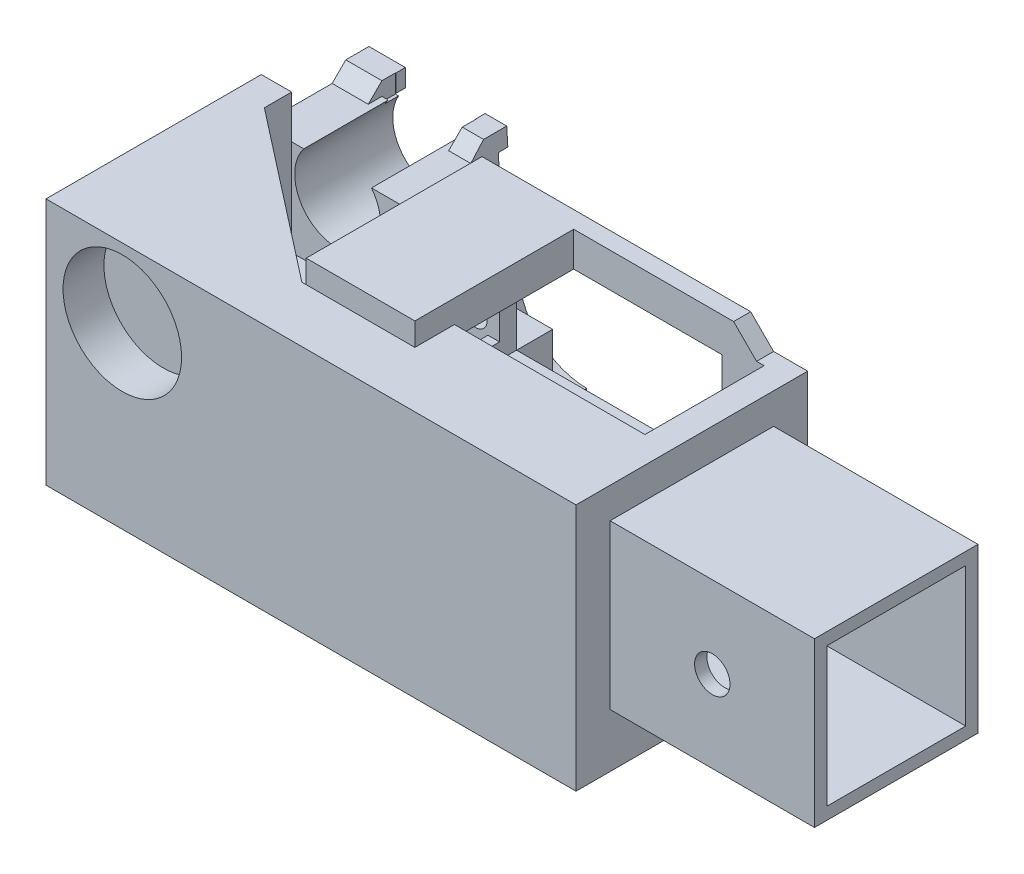
SolidWorks part; units mm, degrees
ref_plane "Front Plane" through (0, 0, 0) normal (0, 0, 1) x (1, 0, 0)
ref_plane "Top Plane" through (0, 0, 0) normal (0, 1, 0) x (1, 0, 0)
ref_plane "Right Plane" through (0, 0, 0) normal (1, 0, 0) x (0, 0, -1)
sketch "Sketch1" plane through (0, 0, 0) normal (0, 0, 1) x (1, 0, 0)
  line L1 (27.178, 17.2339) -> (-27.178, 17.2339)
  line L2 (27.178, 17.2339) -> (27.178, -17.2339)
  line L3 (27.178, -17.2339) -> (-27.178, -17.2339)
  line L4 (-27.178, 17.2339) -> (-27.178, -17.2339)
  line L5 (27.178, 17.2339) -> (-27.178, -17.2339) construction
  line L6 (27.178, -17.2339) -> (-27.178, 17.2339) construction
  line L7 (-27.178, 0) -> (-20.1041, 0) construction
  line L8 (-20.1041, 10.16) -> (-20.1041, -10.16) construction
  line L9 (0, 17.2339) -> (0, 10.16) construction
  line L10 (20.1041, 10.16) -> (-20.1041, 10.16) construction
  line L11 (-27.178, -5.1649) -> (-27.178, 5.1649) construction
  line L13 (20.1041, -10.16) -> (-20.1041, -10.16)
  line L14 (20.1041, -10.16) -> (20.1041, 10.16)
  line L15 (20.1041, 10.16) -> (-20.1041, 10.16)
  line L16 (-20.1041, -10.16) -> (-20.1041, 10.16)
  line L17 (20.1041, -10.16) -> (-20.1041, 10.16) construction
  line L18 (20.1041, 10.16) -> (-20.1041, -10.16) construction
  point P0 (0, 0)
  point P16 (0, 0)
extrude "Boss-Extrude1" add sketch "Sketch1" against normal up to surface (27.94 mm away)
sketch "Sketch2" plane through (0, 0, 0) normal (0, 0, 1) x (1, 0, 0)
  line L0 (20.1041, 10.16) -> (-20.1041, 10.16) construction
  line L1 (22.8981, -12.954) -> (-22.8981, -12.954)
  line L2 (22.8981, -12.954) -> (22.8981, 12.954)
  line L3 (22.8981, 12.954) -> (-22.8981, 12.954)
  line L4 (-22.8981, -12.954) -> (-22.8981, 12.954)
  line L5 (22.8981, -12.954) -> (-22.8981, 12.954) construction
  line L6 (22.8981, 12.954) -> (-22.8981, -12.954) construction
  line L7 (27.178, 17.2339) -> (-27.178, 17.2339)
  line L8 (27.178, 17.2339) -> (27.178, -17.2339)
  line L9 (27.178, -17.2339) -> (-27.178, -17.2339)
  line L10 (-27.178, 17.2339) -> (-27.178, -17.2339)
  line L11 (27.178, 17.2339) -> (-27.178, -17.2339) construction
  line L12 (27.178, -17.2339) -> (-27.178, 17.2339) construction
  line L13 (-20.1041, 10.16) -> (-20.1041, -10.16) construction
  point P0 (0, 0)
  point P6 (0, 0)
  dimension "D1" = 2.794
  dimension "D2" = 2.794
extrude "Cut-Extrude1" cut sketch "Sketch2" against normal offset from surface (24.765 mm away) 3.175 up to face at (0, 0, -27.94)
sketch "Sketch3" plane through (0, 0, -27.94) normal (0, 0, -1) x (-1, 0, 0)
  circle A0 centre (-25.146, 5.6769) radius 2.0497
  circle A1 centre (-25.146, -5.6769) radius 2.0955
  circle A2 centre (25.146, -5.6769) radius 2.0955
  circle A3 centre (25.146, 5.6769) radius 2.0955
extrude "Cut-Extrude2" cut sketch "Sketch3" against normal through all
sketch "Sketch4" plane through (22.8981, 0, 0) normal (1, 0, 0) x (0, 0, -1)
  line L0 (0, -12.954) -> (0, 12.954) construction
  line L1 (2.54, 4.7625) -> (21.59, 4.7625)
  line L2 (2.54, 4.7625) -> (2.54, -4.7625)
  line L3 (2.54, -4.7625) -> (21.59, -4.7625)
  line L4 (21.59, 4.7625) -> (21.59, -4.7625)
  point P4 (2.54, 0)
  dimension "D1" = 19.05
  dimension "D2" = 9.525
  dimension "D3" = 2.54
extrude "Cut-Extrude3" cut sketch "Sketch4" against normal blind 12.7
sketch "Sketch5" plane through (0, 0, 0) normal (0, 0, 1) x (1, 0, 0)
  line L1 (-22.8981, 12.954) -> (22.8981, 12.954)
  line L2 (-22.8981, 12.954) -> (-22.8981, -12.954)
  line L3 (-22.8981, -12.954) -> (22.8981, -12.954)
  line L4 (22.8981, 12.954) -> (22.8981, -12.954)
extrude "Boss-Extrude2" add sketch "Sketch5" along normal blind 2.54
sketch "Sketch6" plane through (0, 0, 2.54) normal (0, 0, 1) x (1, 0, 0)
  line L11 (-22.8981, -12.954) -> (22.8981, -12.954) construction
  line L12 (-12.7, -12.954) -> (12.7, -12.954)
  line L13 (-12.7, -12.954) -> (-12.7, -17.2339)
  line L14 (-12.7, -17.2339) -> (12.7, -17.2339)
  line L15 (12.7, -12.954) -> (12.7, -17.2339)
  line L16 (-27.178, -17.2339) -> (27.178, -17.2339) construction
  point P0 (0, -12.954)
  dimension "D1" = 25.4
extrude "Boss-Extrude3" add sketch "Sketch6" against normal up to surface (27.305 mm away) up to face at (0.0038, 0, -24.765)
sketch "Sketch7" plane through (0, 0, 2.54) normal (0, 0, 1) x (1, 0, 0)
  line L1 (-12.7, -17.2339) -> (12.7, -17.2339)
  line L2 (-12.7, -17.2339) -> (-12.7, -10.8839)
  line L3 (-12.7, -10.8839) -> (12.7, -10.8839)
  line L4 (12.7, -17.2339) -> (12.7, -10.8839)
  dimension "D1" = 25.4
  dimension "D2" = 6.35
extrude "Boss-Extrude4" add sketch "Sketch7" along normal blind 19.05
sketch "Sketch10" plane through (0, -10.8839, 0) normal (0, 1, 0) x (1, 0, 0)
  line L0 (22.8981, -2.54) -> (-22.8981, -2.54) construction
  line L1 (12.7, -21.59) -> (9.525, -21.59)
  line L2 (12.7, -21.59) -> (12.7, -2.54)
  line L3 (12.7, -2.54) -> (9.525, -2.54)
  line L4 (9.525, -21.59) -> (9.525, -2.54)
  line L6 (-12.7, -21.59) -> (-9.525, -21.59)
  line L7 (-12.7, -21.59) -> (-12.7, -2.54)
  line L8 (-12.7, -2.54) -> (-9.525, -2.54)
  line L9 (-9.525, -21.59) -> (-9.525, -2.54)
  dimension "D1" = 3.175
extrude "Boss-Extrude5" add sketch "Sketch10" along normal blind 19.05
chamfer "Chamfer1" distance 19.05 angle 45 2 edges at (-11.1125, 8.1661, 21.59) (11.1125, 8.1661, 21.59)
sketch "Sketch12" plane through (0, -17.2339, 0) normal (0, -1, 0) x (1, 0, 0)
  line L1 (-3.81, 3.81) -> (3.81, 3.81)
  line L2 (-3.81, 3.81) -> (-3.81, -27.94)
  line L3 (-3.81, -27.94) -> (3.81, -27.94)
  line L4 (3.81, 3.81) -> (3.81, -27.94)
  line L5 (-27.178, -27.94) -> (27.178, -27.94) construction
  point P8 (0, 3.81)
  dimension "D1" = 7.62
  dimension "D2" = 31.75
extrude "Boss-Extrude6" add sketch "Sketch12" along normal blind 3.175
sketch "Sketch13" plane through (0, 0, -27.94) normal (0, 0, -1) x (-1, 0, 0)
  line L0 (-20.1041, 10.16) -> (20.1041, 10.16) construction
  line L1 (20.7391, -10.795) -> (-20.7391, -10.795)
  line L2 (20.7391, -10.795) -> (20.7391, 10.795)
  line L3 (20.7391, 10.795) -> (-20.7391, 10.795)
  line L4 (-20.7391, -10.795) -> (-20.7391, 10.795)
  line L5 (20.7391, -10.795) -> (-20.7391, 10.795) construction
  line L6 (20.7391, 10.795) -> (-20.7391, -10.795) construction
  line L7 (-20.1041, -10.16) -> (-20.1041, 10.16) construction
  point P0 (0, 0)
  dimension "D1" = 0.635
  dimension "D2" = 0.635
extrude "Cut-Extrude7" cut sketch "Sketch13" against normal offset from surface (27.94 mm away) 2.54 up to face at (0, -1.251, 2.54)
sketch "Sketch14" plane through (-22.8981, 0, 0) normal (-1, 0, 0) x (0, 0, 1)
  line L0 (21.59, -10.8839) -> (21.59, -17.2339) construction
  line L5 (-24.765, 12.954) -> (-2.54, 12.954)
  line L6 (-24.765, 12.954) -> (-24.765, -7.874)
  line L7 (-24.765, -7.874) -> (-2.54, -7.874)
  line L8 (-2.54, 12.954) -> (-2.54, -7.874)
  line L9 (2.54, 12.954) -> (2.54, -12.954) construction
  line L10 (-24.765, -12.954) -> (2.54, -12.954) construction
  line L11 (-27.94, -20.4089) -> (21.59, -20.4089)
  line L12 (-27.94, -20.4089) -> (-27.94, -12.954)
  line L13 (-27.94, -12.954) -> (21.59, -12.954)
  line L14 (21.59, -20.4089) -> (21.59, -12.954)
  dimension "D1" = 5.08
  dimension "D2" = 5.08
extrude "Cut-Extrude8" cut sketch "Sketch14" against normal through all
sketch "Sketch15" plane through (-27.178, 0, 0) normal (-1, 0, 0) x (0, 0, 1)
  line L1 (-24.765, -12.954) -> (-27.94, -12.954)
  line L2 (-24.765, -12.954) -> (-24.765, -17.2339)
  line L3 (-24.765, -17.2339) -> (-27.94, -17.2339)
  line L4 (-27.94, -12.954) -> (-27.94, -17.2339)
extrude "Cut-Extrude9" cut sketch "Sketch15" against normal through all
sketch "Sketch16" plane through (0, -12.954, 0) normal (0, -1, 0) x (1, 0, 0)
  line L0 (27.178, -27.94) -> (-27.178, -27.94) construction
  line L1 (-22.8981, 2.54) -> (22.8986, 2.54)
  line L2 (-22.8981, 2.54) -> (-22.8981, -27.94)
  line L3 (-22.8981, -27.94) -> (22.8986, -27.94)
  line L4 (22.8986, 2.54) -> (22.8986, -27.94)
extrude "Boss-Extrude7" add sketch "Sketch16" along normal blind 20.32
sketch "Sketch17" plane through (0, 0, -27.94) normal (0, 0, -1) x (-1, 0, 0)
  line L0 (22.8981, -12.954) -> (27.178, -12.954) construction
  line L1 (22.8981, -12.954) -> (65.278, -12.954)
  line L2 (22.8981, -12.954) -> (22.8981, -33.274)
  line L3 (22.8981, -33.274) -> (65.278, -33.274)
  line L4 (65.278, -12.954) -> (65.278, -33.274)
  line L5 (22.8981, -33.274) -> (22.8981, -12.954) construction
  line L6 (27.178, -6.1889) -> (27.178, -12.954) construction
  line L7 (22.8981, -33.274) -> (-22.8986, -33.274) construction
  dimension "D1" = 38.1
extrude "Boss-Extrude8" add sketch "Sketch17" along normal blind 15.24 and the other way blind 10.16 separate body
sketch "Sketch18" plane through (0, -12.954, 0) normal (0, 1, 0) x (1, 0, 0)
  line L1 (-65.278, 43.18) -> (-37.051, 43.18)
  line L2 (-65.278, 43.18) -> (-65.278, 24.9005)
  line L4 (-37.051, 43.18) -> (-37.051, 24.9005)
  line L5 (-37.051, 24.9005) -> (-65.278, 24.9005)
  dimension "D1" = 28.227
extrude "Boss-Extrude9" add sketch "Sketch18" along normal blind 17.8712
sketch "Sketch19" plane through (0, 0, -43.18) normal (0, 0, -1) x (-1, 0, 0)
  line L0 (27.178, 5.1649) -> (27.178, -5.1649) construction
  circle A0 centre (51.054, 0) radius 8.001
  point P4 (27.178, 0)
  dimension "D1" = 16.002
  dimension "D2" = 23.876
extrude "Cut-Extrude10" cut sketch "Sketch19" against normal up to next (18.2795 mm away)
sketch "Sketch20" plane through (-22.8981, 0, 0) normal (-1, 0, 0) x (0, 0, 1)
  line L0 (2.54, 8.1661) -> (2.54, -12.954) construction
  line L1 (2.54, 8.1661) -> (21.59, 8.1661)
  line L2 (2.54, 8.1661) -> (2.54, -12.954)
  line L3 (2.54, -12.954) -> (21.59, -12.954)
  line L4 (21.59, 8.1661) -> (21.59, -12.954)
  line L5 (21.59, -10.8839) -> (2.54, 8.1661) construction
extrude "Cut-Extrude11" cut sketch "Sketch20" against normal through all
sketch "Sketch21" plane through (0, 0, 2.54) normal (0, 0, 1) x (1, 0, 0)
  line L1 (22.8986, -33.274) -> (-22.8981, -33.274)
  line L2 (22.8986, -33.274) -> (22.8986, 12.954)
  line L3 (22.8986, 12.954) -> (-22.8981, 12.954)
  line L4 (-22.8981, -33.274) -> (-22.8981, 12.954)
extrude "Boss-Extrude10" add sketch "Sketch21" along normal blind 12.7
sketch "Sketch25" plane through (0, 0, -27.94) normal (0, 0, -1) x (-1, 0, 0)
  line L0 (-22.8986, -33.274) -> (-22.8986, -12.954) construction
  line L1 (-27.178, 17.2339) -> (-33.528, 17.2339)
  line L2 (-27.178, 17.2339) -> (-27.178, 9.6139)
  line L3 (-27.178, 9.6139) -> (-33.528, 9.6139)
  line L4 (-33.528, 17.2339) -> (-33.528, 9.6139)
  line L5 (-22.8986, -33.274) -> (-33.528, -33.274)
  line L6 (-22.8986, -33.274) -> (-22.8986, -8.1661)
  line L7 (-22.8986, -8.1661) -> (-33.528, -8.1661)
  line L8 (-33.528, -33.274) -> (-33.528, -8.1661)
  line L9 (-27.178, -12.954) -> (-27.178, -6.1889) construction
  line L10 (22.8981, -33.274) -> (-22.8986, -33.274) construction
  dimension "D1" = 7.62
  dimension "D3" = 6.35
  dimension "D4" = 6.35
  dimension "D5" = 17.78
extrude "Boss-Extrude12" add sketch "Sketch25" against normal up to surface (3.175 mm away) up to face at (1.0926, -1.9147, -24.765)
sketch "Sketch26" plane through (0, 0, 15.24) normal (0, 0, 1) x (1, 0, 0)
  line L1 (22.8986, -33.274) -> (33.528, -33.274)
  line L2 (22.8986, -33.274) -> (22.8986, 17.2339)
  line L3 (22.8986, 17.2339) -> (33.528, 17.2339)
  line L4 (33.528, -33.274) -> (33.528, 17.2339)
extrude "Boss-Extrude14" add sketch "Sketch26" against normal up to surface (17.78 mm away) up to face at (0, 2.0002, -2.54)
sketch "Sketch27" plane through (0, 0, -24.765) normal (0, 0, 1) x (1, 0, 0)
  line L0 (33.528, 17.2339) -> (-27.178, 17.2339) construction
  line L1 (33.528, -33.274) -> (28.5856, -33.274)
  line L2 (33.528, -33.274) -> (33.528, 17.2339)
  line L3 (33.528, 17.2339) -> (28.5856, 17.2339)
  line L4 (28.5856, -33.274) -> (28.5856, 17.2339)
extrude "Boss-Extrude15" add sketch "Sketch27" along normal up to surface and the other way up to surface
sketch "Sketch28" plane through (0, -7.874, 0) normal (0, 1, 0) x (1, 0, 0)
  line L1 (20.7391, 24.765) -> (28.5856, 24.765)
  line L2 (20.7391, 24.765) -> (20.7391, 2.54)
  line L3 (20.7391, 2.54) -> (28.5856, 2.54)
  line L4 (28.5856, 24.765) -> (28.5856, 2.54)
extrude "Boss-Extrude16" add sketch "Sketch28" against normal up to surface (25.4 mm away) up to face at (5.3149, -33.274, -6.35)
sketch "Sketch29" plane through (33.528, 0, 0) normal (1, 0, 0) x (0, 0, -1)
  line L0 (-15.24, 17.2339) -> (27.94, 17.2339) construction
  line L1 (-8.89, 7.22) -> (21.59, 7.22)
  line L2 (-8.89, 7.22) -> (-8.89, -23.26)
  line L3 (-8.89, -23.26) -> (21.59, -23.26)
  line L4 (21.59, 7.22) -> (21.59, -23.26)
  line L5 (-15.24, -33.274) -> (-15.24, 17.2339) construction
  point P4 (6.35, 7.22)
  point P7 (6.35, 17.2339)
  point P8 (21.59, -8.02)
  point P11 (-15.24, -8.02)
  dimension "D1" = 30.48
  dimension "D2" = 30.48
extrude "Boss-Extrude17" add sketch "Sketch29" along normal blind 38.1
sketch "Sketch30" plane through (71.628, 0, 0) normal (1, 0, 0) x (0, 0, -1)
  line L0 (21.59, 7.22) -> (-8.89, 7.22) construction
  line L1 (-6.604, 4.934) -> (19.304, 4.934)
  line L2 (-6.604, 4.934) -> (-6.604, -20.974)
  line L3 (-6.604, -20.974) -> (19.304, -20.974)
  line L4 (19.304, 4.934) -> (19.304, -20.974)
  line L5 (-8.89, 7.22) -> (-8.89, -23.26) construction
  point P4 (6.35, 4.934)
  point P7 (6.35, 7.22)
  point P10 (-8.89, -8.02)
  point P11 (-6.604, -8.02)
  dimension "D1" = 25.908
  dimension "D2" = 25.908
extrude "Cut-Extrude13" cut sketch "Sketch30" against normal blind 38.1
sketch "Sketch31" plane through (0, 0, -21.59) normal (0, 0, -1) x (-1, 0, 0)
  line L0 (-33.528, -23.2601) -> (-33.528, 7.2199) construction
  line L2 (-71.628, 7.2199) -> (-33.528, 7.2199) construction
  circle A0 centre (-52.578, -8.0201) radius 3.302
  dimension "D1" = 6.604
  dimension "D2" = 19.05
  dimension "D3" = 15.24
extrude "Cut-Extrude14" cut sketch "Sketch31" against normal through all
sketch "Sketch33" plane through (0, -33.274, 0) normal (0, -1, 0) x (1, 0, 0)
  line L0 (-65.278, -17.78) -> (-22.8981, 15.24)
  line L1 (-22.8981, 15.24) -> (-22.8981, -17.78)
  line L2 (-22.8981, -17.78) -> (-65.278, -17.78)
extrude "Boss-Extrude18" add sketch "Sketch33" against normal up to surface (20.32 mm away) up to face at (-41.7424, -12.954, -28.6202)
sketch "Sketch34" plane through (0, -10.795, 0) normal (0, 1, 0) x (1, 0, 0)
  line L0 (-27.9781, 19.8205) -> (-59.6315, 19.8205)
  line L1 (-15.6591, 7.62) -> (15.6591, 7.62)
  line L2 (-15.6591, 7.62) -> (-15.6591, 19.8205)
  line L3 (-15.6591, 19.8205) -> (15.6591, 19.8205)
  line L4 (15.6591, 7.62) -> (15.6591, 19.8205)
  line L7 (-27.9781, -4.842) -> (-27.9781, 19.8205)
  line L8 (-22.8981, 24.765) -> (-22.8981, 2.54) construction
  line L9 (-59.6315, 19.8205) -> (-27.9781, -4.842)
  line L10 (-22.8981, -15.24) -> (-22.8981, 24.765) construction
  line L11 (-65.278, 24.9005) -> (-37.051, 24.9005) construction
  line L12 (-22.8981, -15.24) -> (-65.278, 17.78) construction
  line L14 (-20.7391, 24.765) -> (-20.7391, 2.54) construction
  line L15 (20.7391, 2.54) -> (20.7391, 24.765) construction
  line L16 (22.8981, 2.54) -> (-22.8981, 2.54) construction
  dimension "D1" = 5.08
  dimension "D2" = 5.08
  dimension "D3" = 5.08
  dimension "D4" = 5.08
  dimension "D5" = 5.08
  dimension "D6" = 5.08
extrude "Cut-Extrude15" cut sketch "Sketch34" against normal through all
sketch "Sketch36" plane through (0, -33.274, 0) normal (0, -1, 0) x (1, 0, 0)
  line L1 (-65.278, -17.78) -> (-65.278, 15.24)
  line L2 (-65.278, 15.24) -> (-22.8981, 15.24)
  line L3 (-59.6315, -19.8205) -> (-27.9781, 4.842)
  line L5 (-22.8981, 8.8001) -> (-22.8981, 15.24)
  line L7 (-65.278, -17.78) -> (-65.278, -43.18) construction
  line L8 (-65.278, -19.8205) -> (-65.278, -17.78)
  line L9 (-27.9781, 4.842) -> (-22.8981, 4.842)
  line L11 (-59.6315, -19.8205) -> (-59.6315, -24.9005)
  line L12 (-59.6315, -24.9005) -> (-65.278, -24.9005)
  line L13 (-65.278, -19.8205) -> (-65.278, -24.9005)
  line L14 (-22.8981, 15.24) -> (-22.8981, -24.765) construction
  line L15 (-22.8981, 4.842) -> (-22.8981, 8.8001)
extrude "Boss-Extrude22" add sketch "Sketch36" against normal up to surface (46.228 mm away) up to face at (7.6329, 12.954, 5.08)
sketch "Sketch37" plane through (0, 0, 15.24) normal (0, 0, 1) x (1, 0, 0)
  circle A0 centre (-51.054, 0) radius 11.049
  arc A1 (-57.3657, 4.9172) -> (-44.7423, 4.9172) centre (-51.054, 0) ccw construction
  dimension "D1" = 22.098
extrude "Cut-Extrude16" cut sketch "Sketch37" against normal blind 7.62
sketch "Sketch38" plane through (0, 0, -24.765) normal (0, 0, 1) x (1, 0, 0)
  line L0 (20.7391, 10.795) -> (-20.7391, 10.795) construction
  line L1 (-27.178, 17.2339) -> (-6.913, 17.2339)
  line L2 (-27.178, 17.2339) -> (-27.178, 10.795)
  line L3 (-27.178, 10.795) -> (-6.913, 10.795)
  line L4 (-6.913, 17.2339) -> (-6.913, 10.795)
extrude "Boss-Extrude25" add sketch "Sketch38" along normal up to surface (29.607 mm away) up to face at (-25.4381, 0, 4.842)
sketch "Sketch39" plane through (0, 17.2339, 0) normal (0, 1, 0) x (1, 0, 0)
  line L1 (22.8986, -15.24) -> (33.528, -15.24)
  line L2 (22.8986, -15.24) -> (22.8986, 27.94)
  line L3 (22.8986, 27.94) -> (33.528, 27.94)
  line L4 (33.528, -15.24) -> (33.528, 27.94)
extrude "Cut-Extrude17" cut sketch "Sketch39" against normal up to surface (4.2799 mm away) up to face at (-18.934, 12.954, -2.0513)
sketch "Sketch40" plane through (0, 0, -27.94) normal (0, 0, -1) x (-1, 0, 0)
  line L0 (-22.8986, 12.954) -> (-22.8986, 17.2339)
  line L1 (-22.8986, 17.2339) -> (-27.1785, 12.954)
  line L2 (-22.8986, 12.954) -> (-33.528, 12.954) construction
  line L3 (-27.1785, 12.954) -> (-22.8986, 12.954)
extrude "Boss-Extrude26" add sketch "Sketch40" against normal up to surface (3.175 mm away) up to face at (20.3914, 6.1033, -24.765)
sketch "Sketch42" plane through (0, 0, -43.18) normal (0, 0, -1) x (-1, 0, 0)
  line L0 (65.278, 12.954) -> (65.278, 4.9172) construction
  line L1 (37.051, 4.9172) -> (65.278, 4.9172)
  line L2 (37.051, 4.9172) -> (37.051, 7.4572)
  line L3 (37.051, 7.4572) -> (65.278, 7.4572)
  line L4 (65.278, 4.9172) -> (65.278, 7.4572)
  dimension "D1" = 2.54
extrude "Boss-Extrude27" add sketch "Sketch42" against normal blind 2.54
sketch "Sketch41" plane through (0, 0, -43.18) normal (0, 0, -1) x (-1, 0, 0)
  line L1 (43.561, 4.0321) -> (58.547, 4.0321)
  line L2 (43.561, 4.0321) -> (43.561, 11.6521)
  line L3 (43.561, 11.6521) -> (58.547, 11.6521)
  line L4 (58.547, 4.0321) -> (58.547, 11.6521)
  circle A0 centre (51.054, 0) radius 8.509
  arc M6 (57.3657, 4.9172) -> (44.7423, 4.9172) centre (51.054, 0) cw
  line M15 (44.7423, 4.9172) -> (57.3657, 4.9172)
  line M16 (44.7423, 4.9172) -> (57.3657, 4.9172)
  dimension "D1" = 17.018
  dimension "D2" = 14.986
  dimension "D3" = 7.62
extrude "Cut-Extrude18" cut sketch "Sketch41" against normal blind 2.54 and the other way blind 7.62 contours A0 L4 L3 L2 M16 M15 | A0 L1 M16 M15 M6 | L1 M6
sketch "Sketch43" plane through (0, 0, -43.18) normal (0, 0, -1) x (-1, 0, 0)
  line L0 (65.278, -33.274) -> (65.278, 7.4572) construction
  line L1 (37.051, 7.4572) -> (43.6245, 7.4572)
  line L2 (37.051, 7.4572) -> (37.051, 4.1552)
  line L3 (37.051, 4.1552) -> (43.6245, 4.1552)
  line L4 (43.6245, 7.4572) -> (43.6245, 4.1552)
  line L5 (58.4835, 7.4572) -> (65.278, 7.4572)
  line L6 (58.4835, 7.4572) -> (58.4835, 4.1552)
  line L7 (58.4835, 4.1552) -> (65.278, 4.1552)
  line L8 (65.278, 7.4572) -> (65.278, 4.1552)
  line L9 (51.054, 0) -> (51.054, 14.9464) construction
  dimension "D1" = 14.859
  dimension "D2" = 7.4295
  dimension "D3" = 3.302
extrude "Boss-Extrude28" add sketch "Sketch43" along normal blind 1.778
sketch "Sketch44" plane through (-65.278, 0, 0) normal (-1, 0, 0) x (0, 0, 1)
  line L0 (-40.64, 7.4572) -> (-40.64, 4.9172)
  line L1 (-40.64, 4.9172) -> (-38.1, 4.9172)
  line L2 (-40.64, 4.9172) -> (-24.9005, 4.9172) construction
  line L3 (-38.1, 4.9172) -> (-40.64, 7.4572)
  dimension "D1" = 2.54
extrude "Boss-Extrude29" add sketch "Sketch44" against normal up to surface (6.731 mm away) up to face at (-58.547, 5.3418, -41.91)
sketch "Sketch45" plane through (-37.051, 0, 0) normal (1, 0, 0) x (0, 0, -1)
  line L0 (40.64, 4.9172) -> (40.64, 7.4572)
  line L1 (40.64, 7.4572) -> (38.1, 4.9172)
  line L2 (38.1, 4.9172) -> (40.64, 4.9172)
extrude "Boss-Extrude30" add sketch "Sketch45" against normal up to surface (6.51 mm away) up to face at (-43.561, 5.3418, -41.91)
sketch "Sketch46" plane through (0, 0, -43.18) normal (0, 0, -1) x (-1, 0, 0)
  line L0 (22.8981, -12.954) -> (35.5981, -12.954)
  line L1 (37.051, -12.954) -> (22.8981, -12.954) construction
  line L2 (22.8981, -12.954) -> (22.8981, -33.274) construction
  line L3 (22.8981, -12.954) -> (22.8981, -25.654)
  arc A0 (35.5981, -12.954) -> (22.8981, -25.654) centre (22.8981, -12.954) cw
  dimension "D1" = 12.7
extrude "Cut-Extrude19" cut sketch "Sketch46" against normal blind 6.35
sketch "Sketch47" plane through (0, 0, -43.18) normal (0, 0, -1) x (-1, 0, 0)
  line L0 (37.051, 7.4572) -> (39.591, 7.4572)
  line L1 (43.6245, 7.4572) -> (37.051, 7.4572) construction
  line L4 (37.051, -12.954) -> (37.051, 7.4572)
  line L5 (37.051, -12.954) -> (38.321, -12.954)
  line L6 (38.321, -12.954) -> (39.591, 7.4572)
  dimension "D1" = 2.54
  dimension "D2" = 1.27
  dimension "D3" = 20.4112
extrude "Cut-Extrude20" cut sketch "Sketch47" against normal blind 6.35 and the other way blind 6.35
